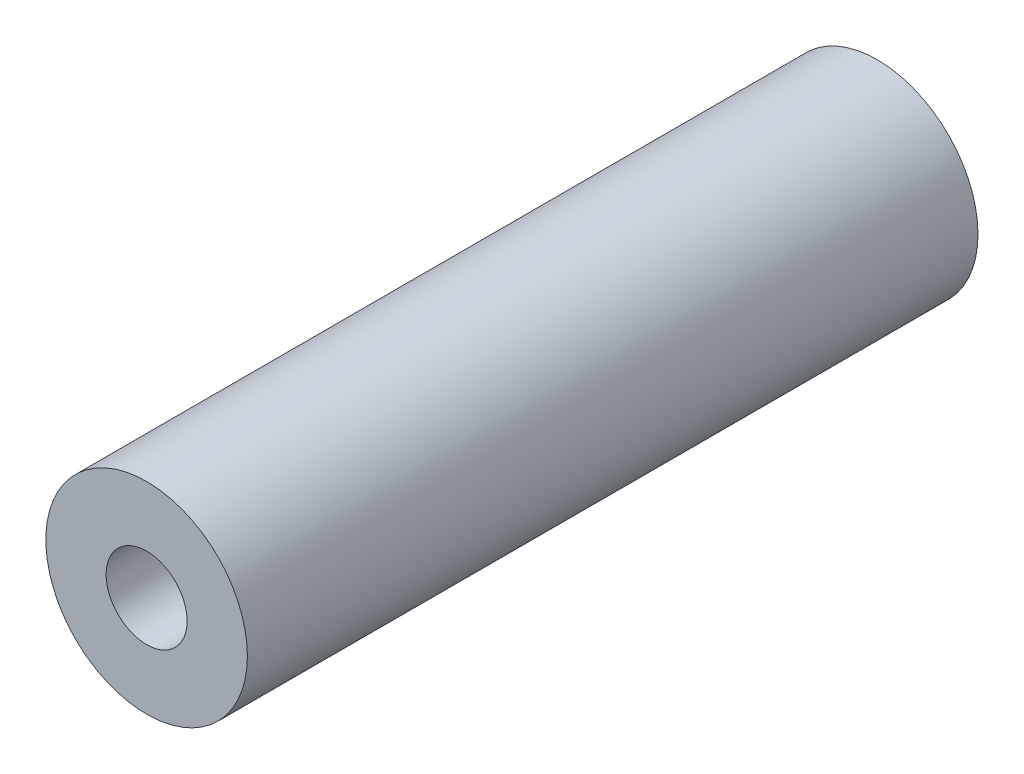
SolidWorks part; units mm, degrees
ref_plane "Front Plane" through (0, 0, 0) normal (0, 0, 1) x (1, 0, 0)
ref_plane "Top Plane" through (0, 0, 0) normal (0, 1, 0) x (1, 0, 0)
ref_plane "Right Plane" through (0, 0, 0) normal (1, 0, 0) x (0, 0, -1)
sketch "Sketch1" plane through (0, 0, 0) normal (0, 0, 1) x (1, 0, 0)
  circle A0 centre (0, 0) radius 2.5527
  circle A1 centre (0, 0) radius 6.35
  dimension "D1" = 5.1054
  dimension "D2" = 12.7
extrude "Boss-Extrude1" add sketch "Sketch1" along normal mid plane 46.0375
